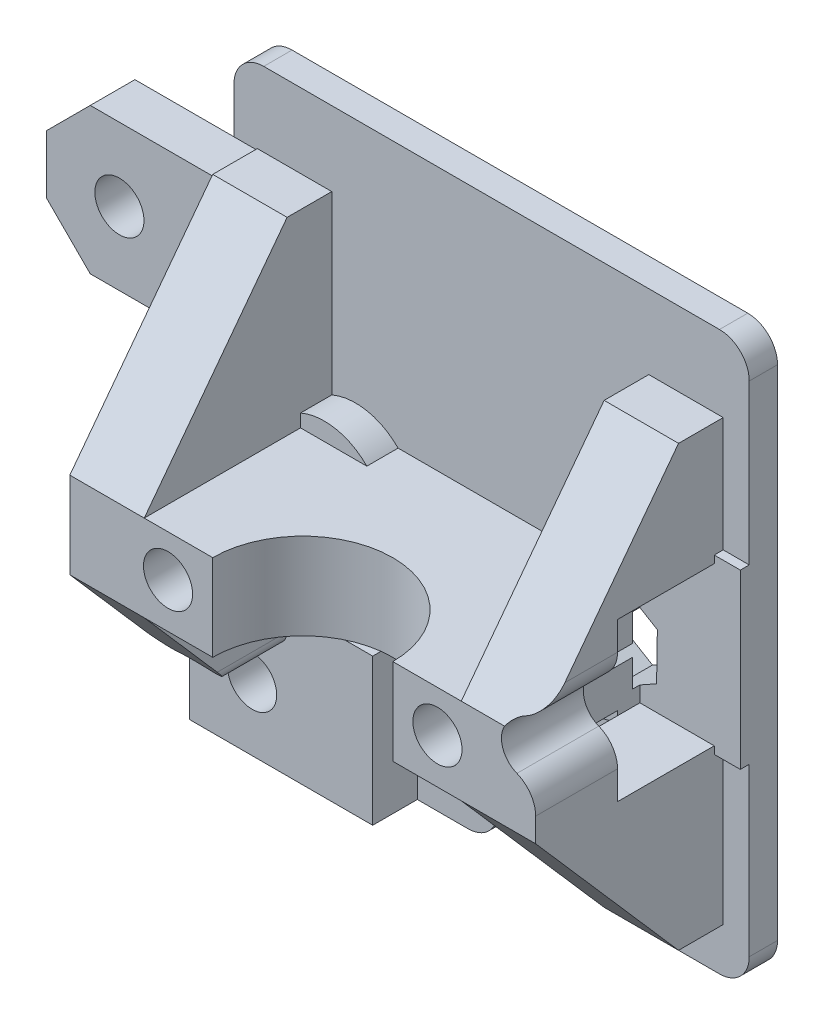
SolidWorks part; units mm, degrees
ref_plane "前视基准面" through (0, 0, 0) normal (0, 0, 1) x (1, 0, 0)
ref_plane "上视基准面" through (0, 0, 0) normal (0, 1, 0) x (1, 0, 0)
ref_plane "右视基准面" through (0, 0, 0) normal (1, 0, 0) x (0, 0, -1)
other "Configuration Table"
sketch "Sketch2" plane through (0, -22.0888, 0) normal (0, -1, 0) x (1, 0, 0)
  line L1 (7.6315, 14.5) -> (2.6315, 14.5)
  line L3 (2.6315, 14.5) -> (1.0315, 14.5)
  line L4 (1.0315, 14.5) -> (1.0315, 0)
  line L5 (1.0315, 0) -> (26.3315, 0)
  line L6 (26.3315, 0) -> (26.3315, 14.5)
  line L7 (26.3315, 14.5) -> (24.7315, 14.5)
  line L9 (24.7315, 14.5) -> (19.7315, 14.5)
  circle A2 centre (13.6815, 14.5) radius 6.05
  arc A3 (7.6315, 14.5) -> (19.7315, 14.5) centre (13.6815, 14.5) ccw
  circle M13 centre (13.6815, 14.5) radius 8
  dimension "D2" = 5
  dimension "D3" = 5
  dimension "D4" = 1.6
  dimension "D5" = 1.6
  dimension "D1" = 0.05
extrude "Boss-Extrude1" add sketch "Sketch2" along normal offset from surface (5.8 mm away) 0.1 from offset 0.1 contours A3 L1 L9 M13 | L9 L1 L3 L4 L5 L6 L7 M13 region at (13.6815, -22.0888, 8.2711) region at (13.6815, -22.0888, 5.7949)
sketch "Sketch4" plane through (0, 0, 0) normal (0, 0, 1) x (1, 0, 0)
  line L61 (5.7815, -39.6388) -> (5.7815, -41.9888)
  line L64 (31.0815, -4.4888) -> (-3.5371, -4.4888)
  line L65 (5.7815, -39.6388) -> (5.7815, -36.3474)
  line L66 (5.7815, -36.3474) -> (2.7229, -33.2888)
  line L67 (2.7229, -33.2888) -> (-3.5371, -33.2888)
  line L68 (-3.5371, -33.2888) -> (-3.5371, -4.4888)
  line L69 (5.7815, -39.6388) -> (5.7815, -36.3474)
  line L70 (5.7815, -36.3474) -> (2.7229, -33.2888)
  line L71 (2.7229, -33.2888) -> (-3.5371, -33.2888)
  line L72 (-3.5371, -33.2888) -> (-3.5371, -4.4888)
  line L73 (31.0815, -4.4888) -> (31.0815, -41.9888)
  line L74 (31.0815, -4.4888) -> (31.0815, -41.9888)
  line L75 (31.0815, -41.9888) -> (5.7815, -41.9888)
  dimension "D2" = 0.1
  dimension "D1" = 0.1
extrude "Boss-Extrude2" add sketch "Sketch4" along normal offset from surface (1.9 mm away) 0.2 offset beyond the face yes
sketch "Sketch5" plane through (0, 0, 1.9) normal (0, 0, 1) x (1, 0, 0)
  line L0 (5.7815, -36.3474) -> (5.7815, -41.9888) construction
  line L19 (-3.7371, -19.3888) -> (-3.7371, -9.5888)
  line L20 (-3.7371, -9.5888) -> (-10.1957, -9.5888)
  line L21 (-10.1957, -9.5888) -> (-13.1371, -12.5302)
  line L22 (-13.1371, -12.5302) -> (-13.1371, -16.4474)
  line L23 (-13.1371, -16.4474) -> (-10.1957, -19.3888)
  line L24 (-10.1957, -19.3888) -> (-3.7371, -19.3888)
  line L26 (-3.7371, -9.5888) -> (-10.1957, -9.5888)
  line L27 (-10.1957, -9.5888) -> (-13.1371, -12.5302)
  line L28 (-13.1371, -12.5302) -> (-13.1371, -16.4474)
  line L29 (-13.1371, -16.4474) -> (-10.1957, -19.3888)
  line L30 (-10.1957, -19.3888) -> (-3.7371, -19.3888)
  line L31 (-3.7371, -9.5888) -> (-0.5371, -9.5888)
  line L32 (-0.5371, -9.5888) -> (-0.5371, -19.3888)
  line L33 (-0.5371, -19.3888) -> (-3.7371, -19.3888)
  line L34 (5.7815, -41.9888) -> (-3.5371, -41.9888)
  line L35 (-3.5371, -33.4888) -> (-3.5371, -32.1433)
  line L36 (-3.5371, -4.4888) -> (-3.5371, -33.2888) construction
  line L37 (2.6401, -42.5388) -> (5.5815, -39.5974)
  line L38 (5.5815, -39.5974) -> (5.5815, -36.4302)
  line L39 (5.5815, -36.4302) -> (2.6401, -33.4888)
  line L40 (2.6401, -33.4888) -> (-3.5371, -33.4888)
  line L41 (-3.5371, -33.4888) -> (-3.5371, -42.5388)
  line L42 (-3.5371, -42.5388) -> (2.6401, -42.5388)
  line L47 (-3.5371, -33.4888) -> (-3.5371, -41.9888)
  line L49 (-3.5371, -32.1433) -> (8.7815, -32.1433)
  line L50 (8.7815, -32.1433) -> (8.7815, -41.9888)
  line L51 (5.7815, -41.9888) -> (31.0815, -41.9888) construction
  line L52 (8.7815, -41.9888) -> (5.7815, -41.9888)
  circle A0 centre (0.6815, -37.6388) radius 1.65
  circle A1 centre (-8.2371, -14.4888) radius 1.65
  dimension "D3" = 3
  dimension "D5" = 3.3
  dimension "D6" = 3.3
  dimension "D4" = 3
  dimension "D1" = 0.1
  dimension "D2" = 0.1
extrude "Boss-Extrude3" add sketch "Sketch5" along normal blind 3
sketch "Sketch6" plane through (0, 0, 1.9) normal (0, 0, 1) x (1, 0, 0)
  line L8 (31.0815, -41.9888) -> (31.0815, -4.4888) construction
  line L10 (26.3815, -27.7888) -> (31.1815, -27.7888) construction
  line L11 (31.0815, -28.7888) -> (25.3815, -28.7888)
  line L12 (31.0815, -28.7888) -> (31.0815, -17.1888)
  line L13 (31.0815, -17.1888) -> (25.3815, -17.1888)
  line L14 (25.3815, -28.7888) -> (25.3815, -17.1888)
  line L15 (26.3815, -18.1888) -> (31.1815, -18.1888) construction
  line L16 (26.3815, -27.7888) -> (26.3815, -18.1888) construction
  dimension "D1" = 1
  dimension "D2" = 1
  dimension "D3" = 1
extrude "Boss-Extrude4" add sketch "Sketch6" along normal up to surface (0.6 mm away)
ref_plane "Plane1" through (13.6815, 0, 0) normal (1, 0, 0) x (0, 0, -1)
sketch "Sketch9" plane through (26.3315, 0, 0) normal (1, 0, 0) x (0, 0, -1)
  line L0 (-1.9, -38.9888) -> (-4.9, -38.9888)
  line L1 (-1.9, -41.9888) -> (-1.9, -28.7888) construction
  line L2 (-4.9, -38.9888) -> (-14.5, -27.9888)
  line L3 (-14.5, -27.9888) -> (-14.5, -22.1888)
  line L4 (-14.5, -22.1888) -> (-4.9, -9.4888)
  line L5 (-4.9, -9.4888) -> (-1.9, -9.4888)
  line L6 (-1.9, -17.1888) -> (-1.9, -4.4888) construction
  line L7 (-1.9, -9.4888) -> (-1.9, -38.9888)
  line L8 (-1.9, -41.9888) -> (0, -41.9888) construction
  line L9 (-1.9, -4.4888) -> (0, -4.4888) construction
  dimension "D1" = 3
  dimension "D2" = 5
  dimension "D3" = 3
  dimension "D4" = 3
extrude "Boss-Extrude5" add sketch "Sketch9" along normal blind 3 and the other way blind 2
sketch "Sketch3" plane through (0, 0, 14.5) normal (0, 0, 1) x (1, 0, 0)
  line L1 (19.7315, -27.9888) -> (19.7315, -22.1888) construction
  line L3 (24.3315, -22.1888) -> (19.7315, -22.1888) construction
  circle A0 centre (22.7315, -24.9888) radius 1.65
  dimension "D1" = 3.3
  dimension "D2" = 3
  dimension "D3" = 2.8
extrude "Cut-Extrude1" cut sketch "Sketch3" against normal blind 50
sketch "Sketch10" plane through (0, 0, 0) normal (0, 0, -1) x (-1, 0, 0)
  circle A0 centre (-22.7315, -24.9888) radius 4
  circle A1 centre (-22.7315, -24.9888) radius 1.65
  dimension "D1" = 8
extrude "Boss-Extrude6" add sketch "Sketch10" against normal blind 4
sketch "Sketch11" plane through (0, 0, 0) normal (0, 0, -1) x (-1, 0, 0)
  line L1 (-22.7831, -21.8138) -> (-25.5069, -23.446)
  line L2 (-25.5069, -23.446) -> (-25.4553, -26.621)
  line L3 (-25.4553, -26.621) -> (-22.6799, -28.1638)
  line L4 (-22.6799, -28.1638) -> (-19.9561, -26.5316)
  line L5 (-19.9561, -26.5316) -> (-20.0077, -23.3566)
  line L6 (-20.0077, -23.3566) -> (-22.7831, -21.8138)
  circle A0 centre (-22.7315, -24.9888) radius 2.75 construction
  dimension "D1" = 5.5
extrude "Cut-Extrude3" cut sketch "Sketch11" against normal blind 3
mirror "Mirror1" about plane through (13.6815, 0, 0) normal (1, 0, 0) of "Cut-Extrude3", "Boss-Extrude6", "Cut-Extrude1", "Boss-Extrude5"
sketch "Sketch13" plane through (0, 0, 1.9) normal (0, 0, -1) x (-1, 0, 0)
  circle A0 centre (-0.6815, -37.6388) radius 1.65
extrude "Cut-Extrude4" cut sketch "Sketch13" against normal blind 10
sketch "Sketch14" plane through (0, 0, 4.9) normal (0, 0, 1) x (1, 0, 0)
  circle A0 centre (0.6815, -37.6388) radius 3.25
  dimension "D1" = 6.5
extrude "Cut-Extrude5" cut sketch "Sketch14" along normal blind 10
fillet "Fillet1" radius 1 2 edges at (3.0315, -35.3938, 6.4687) (-1.9685, -35.7573, 6.3101)
sketch "Sketch15" plane through (29.3315, 0, 0) normal (1, 0, 0) x (0, 0, -1)
  line L0 (-2.5, -28.2888) -> (-9, -28.2888)
  line L1 (-2.5, -28.7888) -> (-2.5, -17.1888) construction
  line L2 (-9, -28.2888) -> (-9, -17.6888)
  line L3 (-9, -17.6888) -> (-2.5, -17.6888)
  line L4 (-2.5, -17.6888) -> (-2.5, -28.2888)
  line L5 (3.5, -27.7888) -> (-4, -27.7888) construction
  line L6 (3.5, -18.1888) -> (-4, -18.1888) construction
  line L7 (-5, -27.7888) -> (-5, -18.1888) construction
  dimension "D1" = 0.5
  dimension "D2" = 0.5
  dimension "D3" = 4
extrude "Cut-Extrude6" cut sketch "Sketch15" against normal blind 5
sketch "Sketch16" plane through (0, 0, 0) normal (0, 0, -1) x (-1, 0, 0)
  line L0 (-14.1815, -40.0888) -> (-14.1815, -41.9888)
  line L1 (-5.7815, -41.9888) -> (-31.0815, -41.9888) construction
  line L2 (-14.1815, -41.9888) -> (-24.1815, -41.9888)
  line L3 (-24.1815, -41.9888) -> (-24.1815, -40.0888)
  arc A0 (-14.1815, -40.0888) -> (-24.1815, -40.0888) centre (-19.1815, -40.0888) ccw
extrude "Cut-Extrude7" cut sketch "Sketch16" against normal blind 10
fillet "Fillet2" radius 2 5 edges at (-3.5371, -4.4888, 0.95) (31.0815, -4.4888, 0.95) (31.0815, -41.9888, 0.95) (24.1815, -41.9888, 0.95) (14.1815, -41.9888, 0.95)
sketch "Sketch17" plane through (0, 0, 14.5) normal (0, 0, 1) x (1, 0, 0)
  circle A0 centre (28.6815, -22.9888) radius 1.65
extrude "Cut-Extrude8" cut sketch "Sketch17" against normal blind 9
fillet "Fillet3" radius 2 2 edges at (29.3315, -21.4722, 11.4792) (29.3315, -24.5054, 11.75)
